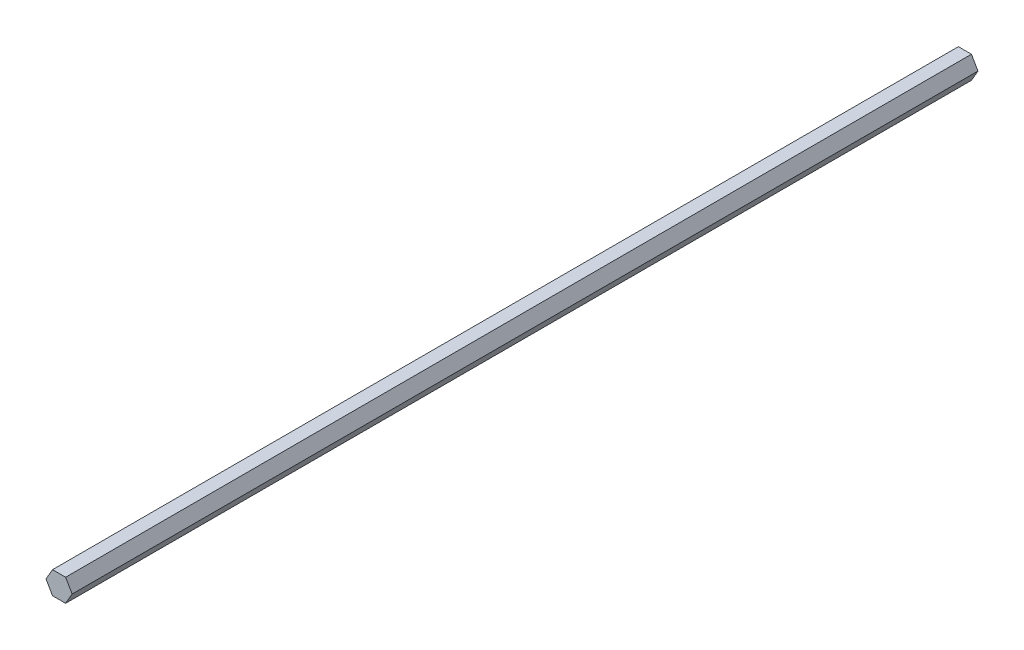
SolidWorks part; units mm, degrees
material "7075-T6 (SN)"
ref_plane "Front Plane" through (0, 0, 0) normal (0, 0, 1) x (1, 0, 0)
ref_plane "Top Plane" through (0, 0, 0) normal (0, 1, 0) x (1, 0, 0)
ref_plane "Right Plane" through (0, 0, 0) normal (1, 0, 0) x (0, 0, -1)
sketch "Sketch1" plane through (0, 0, 0) normal (0, 0, 1) x (1, 0, 0)
  line L0 (-7.3323, 0) -> (7.3323, 0) construction
  line L1 (-3.6662, 6.35) -> (-7.3323, 0)
  line L2 (-7.3323, 0) -> (-3.6662, -6.35)
  line L3 (-3.6662, -6.35) -> (3.6662, -6.35)
  line L4 (3.6662, -6.35) -> (7.3323, 0)
  line L5 (7.3323, 0) -> (3.6662, 6.35)
  line L6 (3.6662, 6.35) -> (-3.6662, 6.35)
  circle A1 centre (0, 0) radius 6.35 construction
  dimension "D1" = 12.7
extrude "Boss-Extrude1" add sketch "Sketch1" along normal blind 508
sketch "Sketch2" plane through (0, 0, 508) normal (0, 0, 1) x (1, 0, 0)
  circle A0 centre (0, 0) radius 6.35
ref_axis "Axis1" through (0, 0, 508) along (0, 0, -1)
